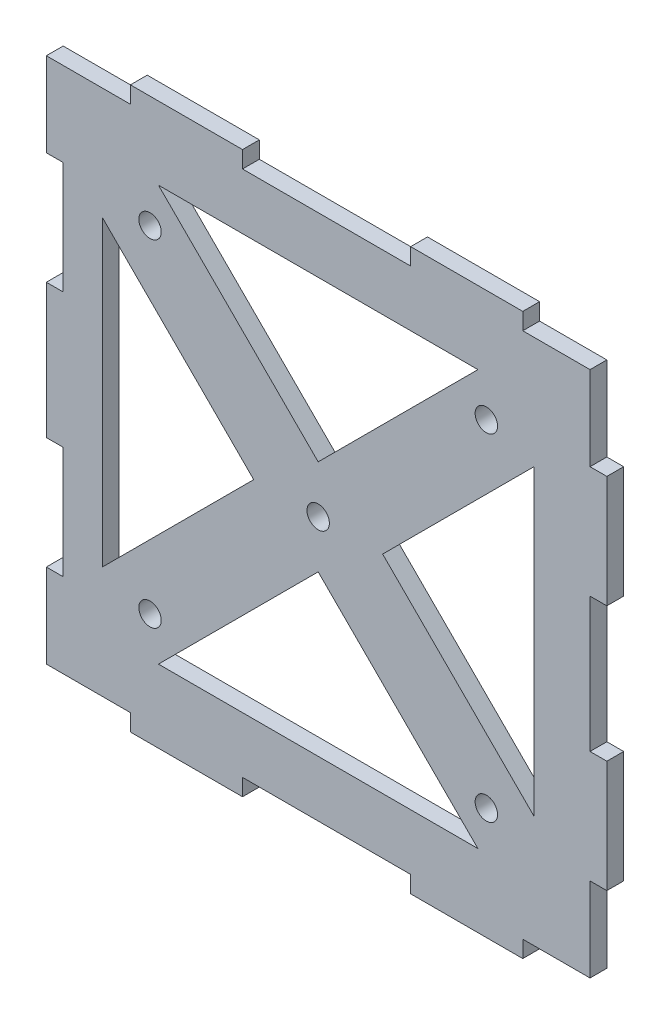
SolidWorks part; units mm, degrees
ref_plane "Plan de face" through (0, 0, 0) normal (0, 0, 1) x (1, 0, 0)
ref_plane "Plan de dessus" through (0, 0, 0) normal (0, 1, 0) x (1, 0, 0)
ref_plane "Plan de droite" through (0, 0, 0) normal (1, 0, 0) x (0, 0, -1)
sketch "Esquisse1" plane through (0, 0, 0) normal (0, 0, 1) x (1, 0, 0)
  line L0 (-36.3514, 95.5523) -> (-36.3514, -4.4477) construction
  line L1 (-84.8514, 97.4275) -> (12.1486, 97.4275)
  line L2 (-84.8514, 97.4275) -> (-84.8514, 3.4275)
  line L3 (-84.8514, 3.4275) -> (12.1486, 3.4275)
  line L4 (12.1486, 97.4275) -> (12.1486, 3.4275)
  line L5 (-74.8514, 87.4275) -> (2.1486, 87.4275)
  line L6 (-74.8514, 87.4275) -> (-74.8514, 13.4275)
  line L7 (-74.8514, 13.4275) -> (2.1486, 13.4275)
  line L8 (2.1486, 87.4275) -> (2.1486, 13.4275)
  line L9 (-94.8547, 50.4275) -> (5.1453, 50.4275) construction
  line L10 (-74.8514, 77.4275) -> (-47.8514, 50.4275)
  line L11 (-64.8514, 87.4275) -> (-36.3514, 58.9275)
  line L12 (-74.8514, 23.4275) -> (-47.8514, 50.4275)
  line L13 (-7.8514, 87.4275) -> (-36.3514, 58.9275)
  line L14 (2.1486, 77.4275) -> (-24.8514, 50.4275)
  line L15 (-64.8514, 13.4275) -> (-36.3514, 41.9275)
  line L16 (-36.3514, 41.9275) -> (-7.8514, 13.4275)
  line L17 (-24.8514, 50.4275) -> (2.1486, 23.4275)
  line L19 (-66.3514, 80.4275) -> (-6.3514, 80.4275) construction
  line L20 (-66.3514, 80.4275) -> (-66.3514, 20.4275) construction
  line L21 (-66.3514, 20.4275) -> (-6.3514, 20.4275) construction
  line L22 (-6.3514, 80.4275) -> (-6.3514, 20.4275) construction
  circle A0 centre (-36.3514, 50.4275) radius 2
  circle A1 centre (-66.3514, 80.4275) radius 2
  circle A2 centre (-6.3514, 80.4275) radius 2
  circle A3 centre (-6.3514, 20.4275) radius 2
  circle A4 centre (-66.3514, 20.4275) radius 2
  point P15 (12.1486, 50.4275)
  point P23 (-36.3514, 3.4275)
  point P36 (-66.3514, 50.4275)
  point P37 (-36.3514, 20.4275)
  dimension "D25" = 4
  dimension "D26" = 4
  dimension "D27" = 4
  dimension "D28" = 4
  dimension "D29" = 4
  dimension "D1" = 97
  dimension "D2" = 94
  dimension "D3" = 10
  dimension "D4" = 10
  dimension "D5" = 10
  dimension "D6" = 10
  dimension "D7" = 45
  dimension "D8" = 45
  dimension "D9" = 10
  dimension "D10" = 10
  dimension "D11" = 45
  dimension "D12" = 10
  dimension "D13" = 45
  dimension "D14" = 10
  dimension "D15" = 45
  dimension "D16" = 10
  dimension "D17" = 10
  dimension "D18" = 10
  dimension "D19" = 10
  dimension "D20" = 45
  dimension "D21" = 45
  dimension "D22" = 45
  dimension "D23" = 0
  dimension "D24" = 0
  dimension "D30" = 0
  dimension "D31" = 0
  dimension "D32" = 60
extrude "Boss.-Extru.1" add sketch "Esquisse1" along normal blind 3 contours L4 L1 L2 L3 L5 L8 L7 L6 | L17 L14 L8 L5 L13 L11 L6 L10 L12 L7 L15 L16 A4 A3 A2 A1 A0 region at (-36.3514, 96.0767, 0) region at (-69.8514, 86.3595, 0)
sketch "Esquisse2" plane through (0, 0, 3) normal (0, 0, 1) x (1, 0, 0)
  line L0 (-84.8514, 50.4275) -> (15.1486, 50.4275) construction
  line L1 (-84.8514, 97.4275) -> (-84.8514, 3.4275) construction
  line L6 (-81.8514, 18.4275) -> (-81.8514, 38.4275)
  line L11 (-84.8514, 82.4275) -> (-81.8514, 82.4275)
  line L12 (-84.8514, 82.4275) -> (-84.8514, 62.4275)
  line L13 (-84.8514, 62.4275) -> (-81.8514, 62.4275)
  line L14 (-81.8514, 82.4275) -> (-81.8514, 62.4275)
  line L15 (-84.8514, 38.4275) -> (-81.8514, 38.4275)
  line L16 (-84.8514, 18.4275) -> (-84.8514, 38.4275)
  line L17 (-84.8514, 18.4275) -> (-81.8514, 18.4275)
  point P12 (-84.8514, 50.4275)
  dimension "D1" = 0
  dimension "D3" = 15
  dimension "D6" = 20
  dimension "D8" = 3
extrude "Enlèv. mat.-Extru.1" cut sketch "Esquisse2" against normal up to next
sketch "Esquisse3" plane through (0, 97.4275, 0) normal (0, 1, 0) x (1, 0, 0)
  line L0 (-84.8514, 0) -> (12.1486, 0) construction
  line L1 (-69.8514, 0) -> (-49.8514, 0)
  line L2 (-69.8514, 0) -> (-69.8514, -3)
  line L3 (-69.8514, -3) -> (-49.8514, -3)
  line L4 (-49.8514, 0) -> (-49.8514, -3)
  line L5 (-84.8514, -3) -> (12.1486, -3) construction
  line L6 (-84.8514, -3) -> (-84.8514, 0) construction
  line L8 (-19.8514, 0) -> (-19.8514, -3)
  line L9 (0.1486, -3) -> (-19.8514, -3)
  line L10 (0.1486, 0) -> (0.1486, -3)
  line L11 (0.1486, 0) -> (-19.8514, 0)
  point P10 (-19.8514, 0)
  dimension "D1" = 15
  dimension "D2" = 20
  dimension "D3" = 30
  dimension "D4" = 20
extrude "Boss.-Extru.2" add sketch "Esquisse3" along normal blind 3
sketch "Esquisse4" plane through (12.1486, 0, 0) normal (1, 0, 0) x (0, 0, -1)
  line L0 (-3, 97.4275) -> (-3, 3.4275) construction
  line L1 (-3, 82.4275) -> (0, 82.4275)
  line L2 (-3, 82.4275) -> (-3, 62.4275)
  line L3 (-3, 62.4275) -> (0, 62.4275)
  line L4 (0, 82.4275) -> (0, 62.4275)
  line L5 (0, 97.4275) -> (0, 3.4275) construction
  line L6 (-3, 97.4275) -> (0, 97.4275) construction
  line L7 (-3, 50.4275) -> (0, 50.4275) construction
  line L8 (0, 18.4275) -> (0, 38.4275)
  line L9 (-3, 38.4275) -> (0, 38.4275)
  line L10 (-3, 18.4275) -> (-3, 38.4275)
  line L11 (-3, 18.4275) -> (0, 18.4275)
  dimension "D1" = 15
  dimension "D2" = 20
extrude "Boss.-Extru.3" add sketch "Esquisse4" along normal blind 3
sketch "Esquisse5" plane through (0, 3.4275, 0) normal (0, -1, 0) x (1, 0, 0)
  line L0 (-84.8514, 3) -> (12.1486, 3) construction
  line L1 (-69.8514, 3) -> (-49.8514, 3)
  line L2 (-69.8514, 3) -> (-69.8514, 0)
  line L3 (-69.8514, 0) -> (-49.8514, 0)
  line L4 (-49.8514, 3) -> (-49.8514, 0)
  line L5 (-84.8514, 0) -> (12.1486, 0) construction
  line L6 (-84.8514, 3) -> (-84.8514, 0) construction
  line L7 (-19.8514, 3) -> (0.1486, 3)
  line L8 (-19.8514, 3) -> (-19.8514, 0)
  line L9 (-19.8514, 0) -> (0.1486, 0)
  line L10 (0.1486, 3) -> (0.1486, 0)
  dimension "D1" = 15
  dimension "D2" = 20
  dimension "D3" = 30
  dimension "D4" = 20
extrude "Boss.-Extru.4" add sketch "Esquisse5" along normal blind 3
